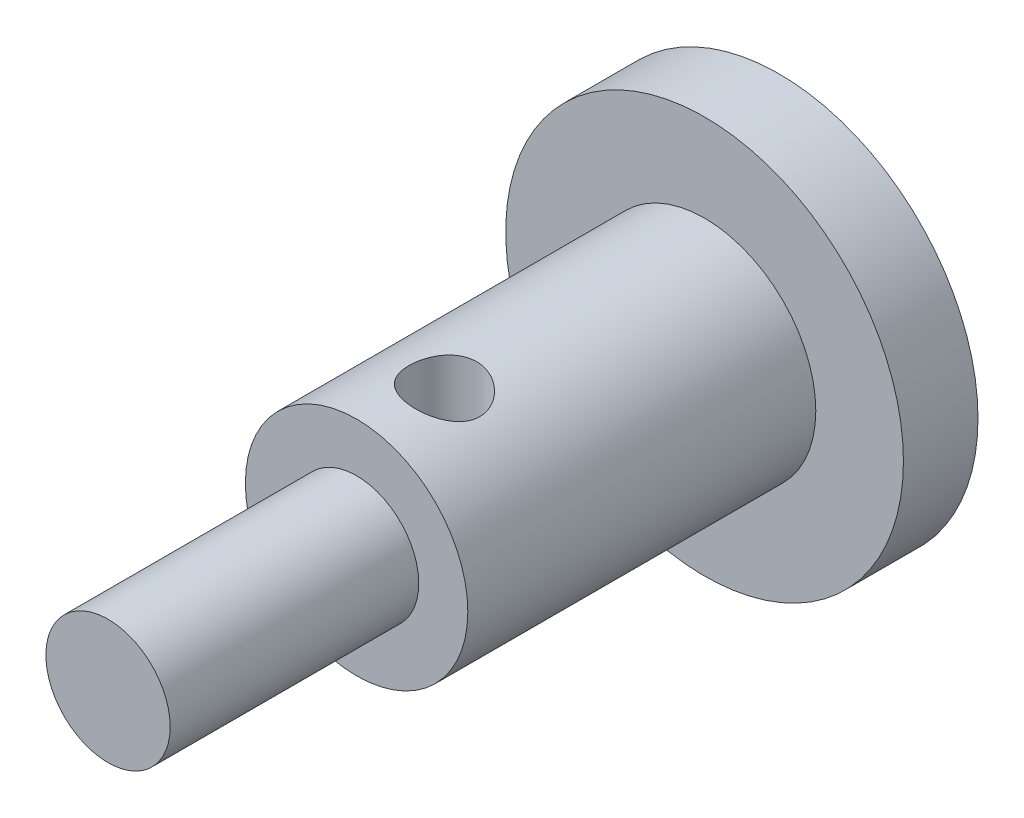
SolidWorks part; units mm, degrees
ref_plane "Front Plane" through (0, 0, 0) normal (0, 0, 1) x (1, 0, 0)
ref_plane "Top Plane" through (0, 0, 0) normal (0, 1, 0) x (1, 0, 0)
ref_plane "Right Plane" through (0, 0, 0) normal (1, 0, 0) x (0, 0, -1)
sketch "Sketch1" plane through (0, 0, 0) normal (0, 0, 1) x (1, 0, 0)
  circle A0 centre (0, 0) radius 8
  dimension "D1" = 16
extrude "Boss-Extrude1" add sketch "Sketch1" along normal blind 3
sketch "Sketch2" plane through (0, 0, 3) normal (0, 0, 1) x (1, 0, 0)
  circle A0 centre (0, 0) radius 4.475
  dimension "D1" = 8.95
extrude "Boss-Extrude2" add sketch "Sketch2" along normal blind 14
sketch "Sketch3" plane through (0, 0, 17) normal (0, 0, 1) x (1, 0, 0)
  circle A0 centre (0, 0) radius 2.5
  dimension "D1" = 5
extrude "Boss-Extrude3" add sketch "Sketch3" along normal blind 10
sketch "Sketch4" plane through (0, 0, 0) normal (0, 1, 0) x (1, 0, 0)
  line L0 (-4.475, -3) -> (-4.475, -17) construction
  circle A0 centre (0.525, -13.9902) radius 1.425
  dimension "D2" = 2.85
  dimension "D1" = 5
  dimension "D3" = 14
extrude "Cut-Extrude1" cut sketch "Sketch4" against normal mid plane 15
equation "\"D1@Sketch2\"= 9.35 - \"tol1@parametersSketch@prostheticParameters.SLDPRT\""
equation "\"D2@Sketch4\"= 2.45 + \"tol1@parametersSketch@prostheticParameters.SLDPRT\""
